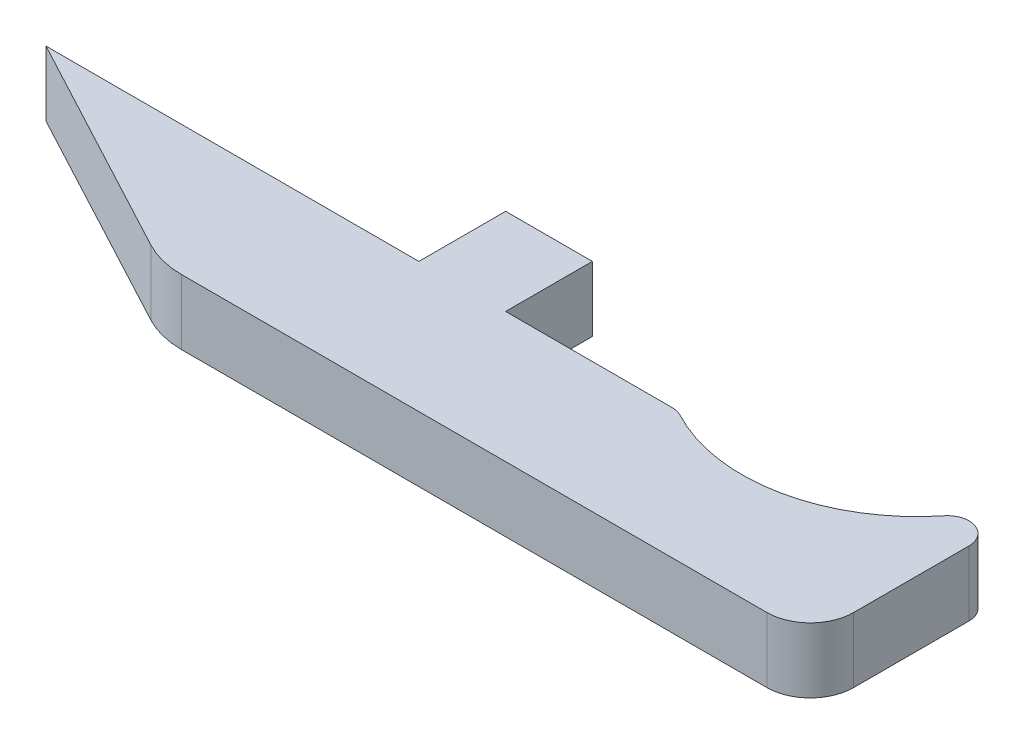
SolidWorks part; units mm, degrees
material "AISI 4130 Steel, annealed at 865C"
ref_plane "X-Y Datum" through (0, 0, 0) normal (0, 0, 1) x (1, 0, 0)
ref_plane "X-Z Datum" through (0, 0, 0) normal (0, 1, 0) x (1, 0, 0)
ref_plane "Y-Z Datum" through (0, 0, 0) normal (1, 0, 0) x (0, 0, -1)
sketch "Sketch1" plane through (0, 0, 0) normal (0, 1, 0) x (1, 0, 0)
  line L0 (58.9432, -34.1434) -> (58.9432, -34.1499) construction
  line L1 (58.9432, -45.2718) -> (3.2156, -45.2718)
  line L2 (58.9432, -45.2718) -> (58.9432, -34.1466)
  line L3 (24.1452, -54.7968) -> (71.7702, -54.7968)
  line L4 (71.7702, -34.1466) -> (71.7702, -54.7968)
  line L5 (6.2845, -45.2718) -> (24.1452, -54.7968)
  line L8 (33.5895, -45.2591) -> (3.1095, -45.2591) construction
  line L9 (33.5895, -45.2591) -> (3.1095, -45.2591)
  circle A0 centre (58.9432, -34.1466) radius 12.827
  circle A1 centre (58.9432, -34.1466) radius 12.7
  circle A2 centre (58.9432, -34.1466) radius 12.7 construction
  dimension "D3" = 25.654
  dimension "D5" = 9.525
  dimension "D1" = 55.7276
  dimension "D2" = 11.1252
  dimension "D4" = 3.175
  dimension "D6" = 47.625
extrude "Boss-Extrude1" add sketch "Sketch1" along normal blind 4.7625 contours L1 A0 region at (43.8554, 0, 49.6141)
fillet "Fillet1" radius 1.5875 2 edges at (52.5587, 2.3813, 45.2718) (71.7702, 2.3813, 34.1466)
fillet "Fillet2" radius 6.35 1 edges at (24.1452, 2.3813, 54.7968)
fillet "Fillet3" radius 3.175 1 edges at (71.7702, 2.3813, 54.7968)
sketch "Sketch2" plane through (0, 0, 45.2718) normal (0, 0, -1) x (-1, 0, 0)
  line L0 (-52.1488, 4.7625) -> (-6.2845, 4.7625) construction
  line L1 (-39.9395, 4.7625) -> (-33.5895, 4.7625)
  line L2 (-39.9395, 4.7625) -> (-39.9395, 0)
  line L3 (-39.9395, 0) -> (-33.5895, 0)
  line L4 (-33.5895, 4.7625) -> (-33.5895, 0)
  line L5 (-52.1488, 0) -> (-6.2845, 0) construction
  line L6 (-6.2845, 4.7625) -> (-6.2845, 0) construction
  dimension "D1" = 27.305
  dimension "D2" = 6.35
extrude "Boss-Extrude2" add sketch "Sketch2" along normal blind 6.35
